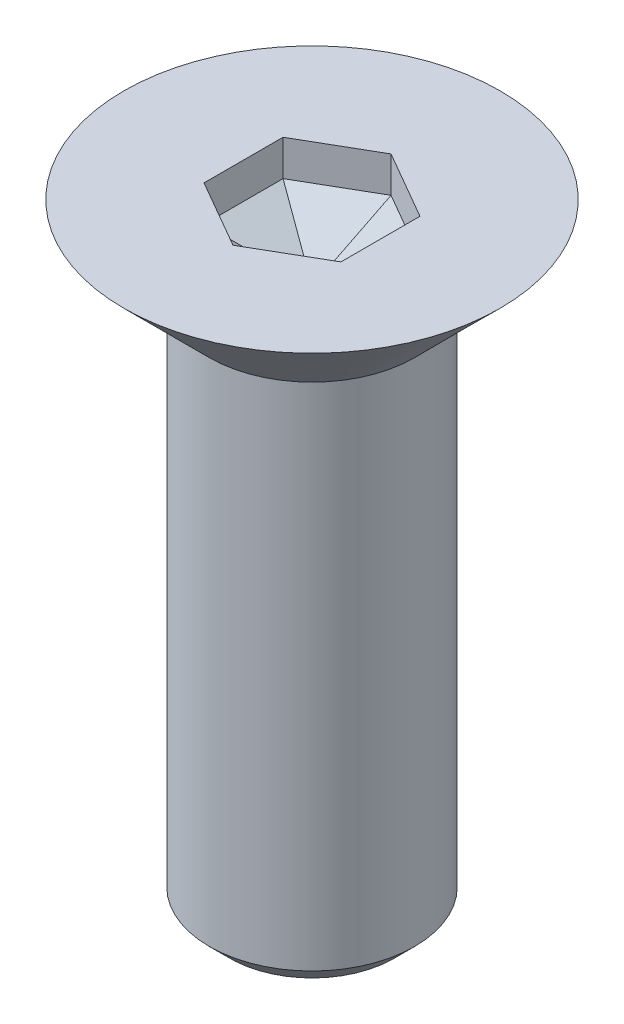
SolidWorks part; units mm, degrees
ref_plane "前视基准面" through (0, 0, 0) normal (0, 0, 1) x (1, 0, 0)
ref_plane "上视基准面" through (0, 0, 0) normal (0, 1, 0) x (1, 0, 0)
ref_plane "右视基准面" through (0, 0, 0) normal (1, 0, 0) x (0, 0, -1)
sketch "草图2" plane through (0, 0, 0) normal (0, 0, 1) x (1, 0, 0)
  line L0 (0, -1.86) -> (0, 0)
  line L1 (0, 0) -> (2.75, 0)
  line L2 (2.75, 0) -> (0.89, -1.86)
  line L3 (0.89, -1.86) -> (0, -1.86)
  dimension "D1" = 45
  dimension "k" = 1.86
  dimension "dk/2" = 2.75
revolve "旋转1" add sketch "草图2" angle 360 about L0
sketch "草图4" plane through (0, 0, 0) normal (0, -1, 0) x (1, 0, 0)
  circle A0 centre (0, 0) radius 1.5
  dimension "d" = 3
extrude "凸台-拉伸2" add sketch "草图4" along normal blind 9
cosmetic thread "装饰螺纹线1" parameters "b"=12, "D2"=2.459
sketch "草图3" plane through (0, 0, 0) normal (0, 1, 0) x (1, 0, 0)
  line L1 (1, 0.5774) -> (0, 1.1547)
  line L2 (0, 1.1547) -> (-1, 0.5774)
  line L3 (-1, 0.5774) -> (-1, -0.5774)
  line L4 (-1, -0.5774) -> (0, -1.1547)
  line L5 (0, -1.1547) -> (1, -0.5774)
  line L6 (1, -0.5774) -> (1, 0.5774)
  circle A0 centre (0, 0) radius 1 construction
  dimension "S" = 2
extrude "切除-拉伸1" cut sketch "草图3" against normal blind 1.1
chamfer "倒角3" distance 0.5764 angle 60 6 edges at (-0.5, -1.1, 0.866) (-1, -1.1, 0) (-0.5, -1.1, -0.866) (0.5, -1.1, -0.866) (1, -1.1, 0) (0.5, -1.1, 0.866) first distance on face at (-0.5, -0.55, 0.866) first distance on face at (-1, -0.55, 0) first distance on face at (-0.5, -0.55, -0.866) first distance on face at (0.5, -0.55, -0.866) first distance on face at (1, -0.55, 0) first distance on face at (0.5, -0.55, 0.866)
chamfer "倒角4" distance 0.3 angle 45 1 edges at (0, -9, -1.5)
ref_axis "基准轴1" through (0, -8.7, 0) along (0, 1, 0)
ref_plane "基准面1" through (0, 0, 0) normal (0, -1, 0) x (-1, 0, 0)
equation "\"D1@倒角3\"= \"S@草图3\" / 3.47"
equation "\"D1@倒角4\"= \"d@草图4\" / 10"
